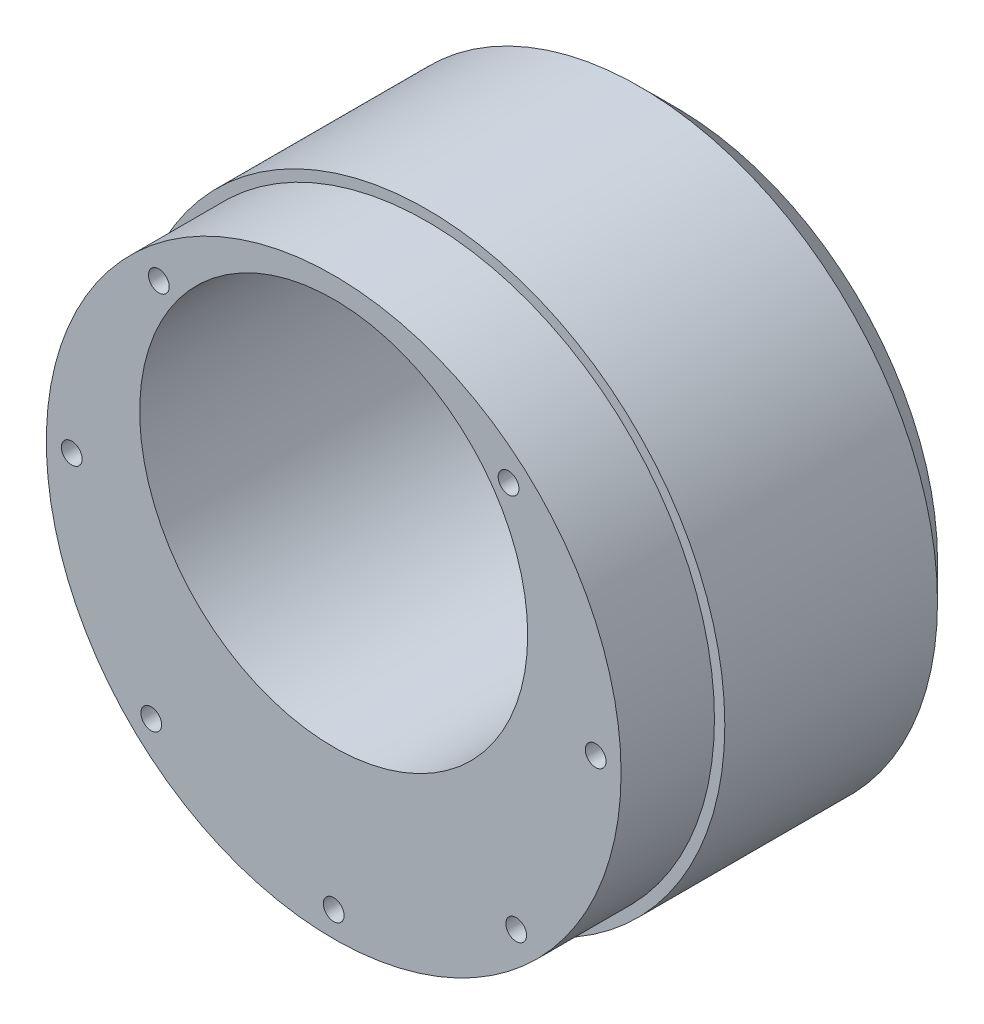
SolidWorks part; units mm, degrees
ref_plane "Спереди" through (0, 0, 0) normal (0, 0, 1) x (1, 0, 0)
ref_plane "Сверху" through (0, 0, 0) normal (0, 1, 0) x (1, 0, 0)
ref_plane "Справа" through (0, 0, 0) normal (1, 0, 0) x (0, 0, -1)
sketch "Sketch1" plane through (0, 0, 0) normal (0, 0, 1) x (1, 0, 0)
  circle A0 centre (0, 0) radius 28.7
  circle A1 centre (0, 0) radius 6.15
  circle A3 centre (0, 7) radius 15.5 construction
  circle A4 centre (15.5, 7) radius 1.65
  circle A5 centre (7.75, -6.4234) radius 1.65
  circle A6 centre (-7.75, -6.4234) radius 1.65
  circle A7 centre (-15.5, 7) radius 1.65
  circle A8 centre (-7.75, 20.4234) radius 1.65
  circle A9 centre (7.75, 20.4234) radius 1.65
  point P20 (0, 7)
  dimension "D1" = 57.4
  dimension "D2" = 12.3
  dimension "D3" = 7
  dimension "D4" = 31
  dimension "D5" = 3.3
  dimension "D6" = 6
extrude "Основа" add sketch "Sketch1" along normal blind 33
sketch "Sketch2" plane through (0, 0, 33) normal (0, 0, 1) x (1, 0, 0)
  circle A0 centre (0, 7) radius 18.7
  dimension "D1" = 37.4
  dimension "D2" = 7
extrude "Посадочное под двигатель" cut sketch "Sketch2" against normal blind 27
sketch "Sketch4" plane through (0, 0, 33) normal (0, 0, 1) x (1, 0, 0)
  circle A0 centre (0, 0) radius 27.7
  circle A1 centre (0, 0) radius 28.7
  circle A2 centre (0, 0) radius 28.7 construction
  dimension "D1" = 55.4
extrude "Вырез под внутреннее кольцо подшипника" cut sketch "Sketch4" against normal blind 9
sketch "Sketch5" plane through (0, 0, 33) normal (0, 0, 1) x (1, 0, 0)
  line L0 (0, 7) -> (0, -25.25) construction
  line L1 (0, 7) -> (-25.2489, 0.2346) construction
  line L2 (0, 7) -> (-17.5875, -18.1175) construction
  line L3 (0, 7) -> (-16.8543, 18.8015) construction
  circle A1 centre (0, 7) radius 18.7 construction
  circle A2 centre (-25.2489, 0.2346) radius 1
  circle A3 centre (-17.5875, -18.1175) radius 1
  circle A4 centre (17.5875, -18.1175) radius 1
  circle A5 centre (25.2489, 0.2346) radius 1
  circle A7 centre (-16.8543, 18.8015) radius 1
  circle A8 centre (16.8543, 18.8015) radius 1
  circle A12 centre (0, 0) radius 25.25 construction
  circle A13 centre (0, 7) radius 18.7 construction
  circle A14 centre (0, -25.25) radius 1
  dimension "D1" = 50.5
  dimension "D4" = 2
  dimension "D5" = 75
  dimension "D2" = 35
  dimension "D3" = 125
extrude "Под шурупы крепления колена" cut sketch "Sketch5" against normal blind 10
chamfer "Chamfer1" distance 3.5 angle 45 1 edges at (28.7, 0, 0)
sketch "Эскиз1" plane through (0, 0, 0) normal (0, 0, -1) x (-1, 0, 0)
  circle A0 centre (-7.75, 20.4234) radius 3
  circle A1 centre (7.75, 20.4234) radius 3
  circle A2 centre (15.5, 7) radius 3
  circle A3 centre (7.75, -6.4234) radius 3
  circle A4 centre (-7.75, -6.4234) radius 3
  circle A5 centre (-15.5, 7) radius 3
  dimension "D1" = 6
extrude "Углубления под шляпки" cut sketch "Эскиз1" against normal blind 2
chamfer "Скругления под шляпки винтов крепления двигателя к стакану" distance 1.5 angle 45 6 edges at (13.85, 7, 2) (6.1, -6.4234, 2) (-9.4, -6.4234, 2) (-17.15, 7, 2) (-9.4, 20.4234, 2) (6.1, 20.4234, 2)
